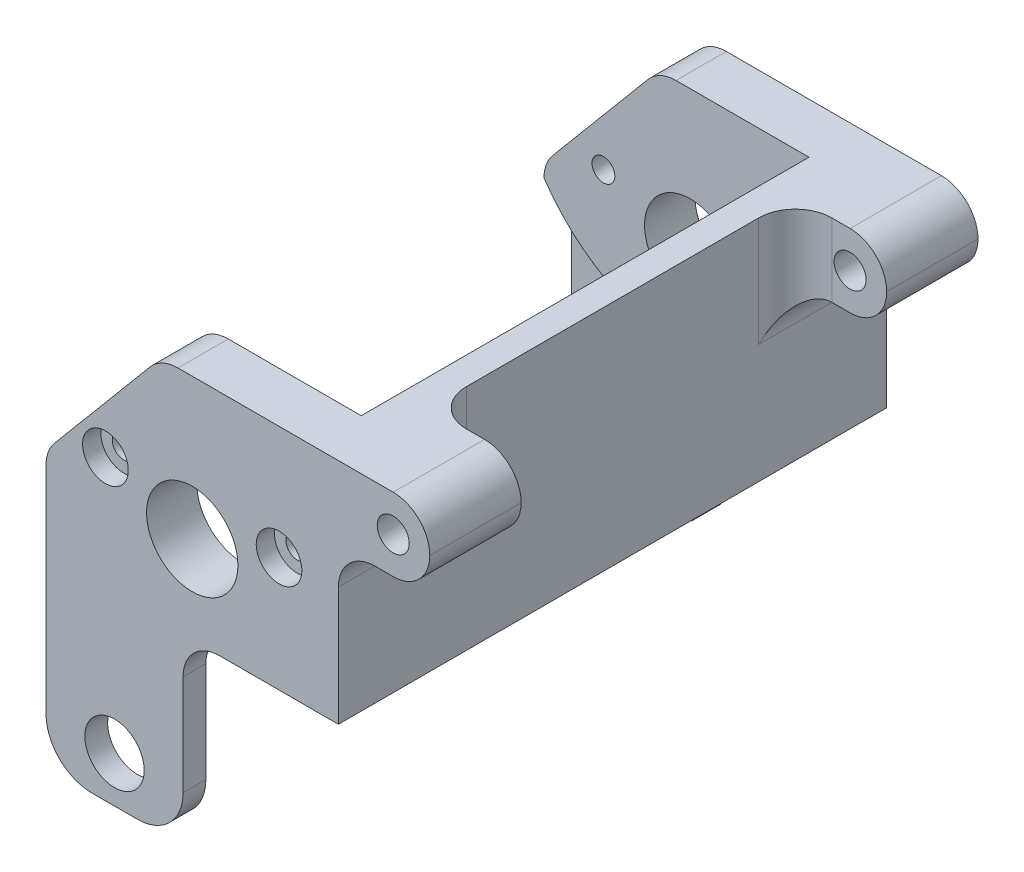
SolidWorks part; units mm, degrees
ref_plane "Front Plane" through (0, 0, 0) normal (0, 0, 1) x (1, 0, 0)
ref_plane "Top Plane" through (0, 0, 0) normal (0, 1, 0) x (1, 0, 0)
ref_plane "Right Plane" through (0, 0, 0) normal (1, 0, 0) x (0, 0, -1)
sketch "Sketch2" plane through (0, 0, 0) normal (0, 0, 1) x (1, 0, 0)
  line L0 (-7.5, 5) -> (-7.5, 30)
  line L1 (-7.5, 30) -> (5.0865, 45)
  line L2 (5.0865, 45) -> (24.5, 45)
  line L3 (24.5, 45) -> (24.5, 20)
  line L4 (24.5, 20) -> (7.5, 20)
  line L5 (7.5, 20) -> (7.5, 5)
  line L6 (-2.5, 0) -> (2.5, 0)
  line L7 (-7.5, 0) -> (7.5, 0) construction
  line L8 (-7.5, 5) -> (7.5, 5) construction
  line L9 (18.0048, 32.5697) -> (-0.9952, 32.5697) construction
  line L10 (8.5048, 32.5697) -> (8.5048, 29.5697) construction
  line L11 (0, 5) -> (8.5048, 29.5697) construction
  circle A5 centre (0, 5) radius 3.25
  circle A6 centre (18.0048, 32.5697) radius 1.25
  circle A7 centre (-0.9952, 32.5697) radius 1.25
  circle A8 centre (8.5048, 29.5697) radius 5
  circle A9 centre (8.5048, 32.5697) radius 12.5 construction
  arc A10 (2.5, 0) -> (7.5, 5) centre (2.5, 5) ccw
  arc A11 (-7.5, 5) -> (-2.5, 0) centre (-2.5, 5) ccw
  dimension "D3" = 6.5
  dimension "D4" = 5
  dimension "D10" = 10
  dimension "D12" = 2.5
  dimension "D14" = 25
  dimension "D15" = 5
  dimension "D1" = 40
  dimension "D2" = 15
  dimension "D5" = 30
  dimension "D6" = 15
  dimension "D7" = 17
  dimension "D8" = 20
  dimension "D9" = 19
  dimension "D11" = 3
  dimension "D13" = 26
extrude "Boss-Extrude1" add sketch "Sketch2" along normal blind 30 and the other way blind 30
sketch "Sketch3" plane through (0, 45, 0) normal (0, 1, 0) x (1, 0, 0)
  line L0 (-7.5, -30) -> (-7.5, 30) construction
  line L1 (-36.5, -27.5) -> (21.5, -27.5)
  line L2 (-36.5, -27.5) -> (-36.5, 27.5)
  line L3 (-36.5, 27.5) -> (21.5, 27.5)
  line L4 (21.5, -27.5) -> (21.5, 27.5)
  line L5 (-36.5, -27.5) -> (21.5, 27.5) construction
  line L6 (-36.5, 27.5) -> (21.5, -27.5) construction
  line L7 (24.5, 30) -> (5.0865, 30) construction
  line L8 (24.5, -30) -> (24.5, 30) construction
  point P0 (-7.5, 0)
  dimension "D1" = 2.5
  dimension "D2" = 3
extrude "Cut-Extrude1" cut sketch "Sketch3" against normal through all
sketch "Sketch4" plane through (24.5, 0, 0) normal (1, 0, 0) x (0, 0, -1)
  line L1 (-30, 45) -> (-20, 45)
  line L2 (-30, 45) -> (-30, 37)
  line L3 (-30, 37) -> (-20, 37)
  line L4 (-20, 45) -> (-20, 37)
  dimension "D1" = 10
  dimension "D2" = 8
extrude "Boss-Extrude2" add sketch "Sketch4" along normal blind 10
fillet "Fillet1" radius 4 2 edges at (34.5, 37, 25) (34.5, 45, 25)
sketch "Sketch5" plane through (0, 0, 20) normal (0, 0, -1) x (-1, 0, 0)
  circle A0 centre (-30.5, 41) radius 1.75
  dimension "D1" = 3.5
extrude "Cut-Extrude2" cut sketch "Sketch5" against normal through all
mirror "Mirror1" about plane through (0, 0, 0) normal (0, 0, 1) of "Cut-Extrude2", "Fillet1", "Boss-Extrude2"
fillet "Fillet2" radius 4 10 edges at (24.5, 41, -20) (24.5, 41, 20) (5.0865, 45, -28.75) (7.5, 20, -28.75) (24.5, 37, -25) (24.5, 37, 25) (7.5, 20, 28.75) (5.0865, 45, 28.75) (-7.5, 30, 28.75) (-7.5, 30, -28.75)
sketch "Sketch6" plane through (0, 0, -27.5) normal (0, 0, 1) x (1, 0, 0)
  line L0 (-0.9952, 32.5697) -> (18.0048, 32.5697) construction
  line L7 (21.5, 45) -> (6.9517, 45)
  line L8 (3.8875, 43.5712) -> (-6.5642, 31.1153)
  line L9 (-7.5, 28.5441) -> (-7.5, 5)
  line L10 (-2.5, 0) -> (2.5, 0)
  line L11 (7.5, 5) -> (7.5, 16)
  line L12 (11.5, 20) -> (21.5, 20)
  line L13 (21.5, 20) -> (21.5, 45)
  line L14 (21.5, 45) -> (6.9517, 45)
  line L15 (3.8875, 43.5712) -> (-6.5642, 31.1153)
  line L19 (11.5, 20) -> (21.5, 20)
  line L20 (21.5, 20) -> (21.5, 45)
  arc A1 (11.5, 20) -> (-7.5, 28.5441) centre (8.8465, 39.497) cw
  circle A2 centre (18.0048, 32.5697) radius 1.25 construction
  circle A3 centre (8.5048, 29.5697) radius 5 construction
  circle A4 centre (-0.9952, 32.5697) radius 1.25 construction
  circle A5 centre (18.0048, 32.5697) radius 1.25
  arc A6 (6.9517, 45) -> (3.8875, 43.5712) centre (6.9517, 41) ccw
  arc A7 (-6.5642, 31.1153) -> (-7.5, 28.5441) centre (-3.5, 28.5441) ccw
  arc A8 (-7.5, 5) -> (-2.5, 0) centre (-2.5, 5) ccw
  arc A9 (2.5, 0) -> (7.5, 5) centre (2.5, 5) ccw
  arc A10 (11.5, 20) -> (7.5, 16) centre (11.5, 16) ccw
  arc A11 (6.9517, 45) -> (3.8875, 43.5712) centre (6.9517, 41) ccw
  arc A12 (-6.5642, 31.1153) -> (-7.5, 28.5441) centre (-3.5, 28.5441) ccw
  circle A16 centre (8.5048, 29.5697) radius 5
  circle A17 centre (-0.9952, 32.5697) radius 1.25
  dimension "D1" = 0
extrude "Boss-Extrude3" add sketch "Sketch6" along normal blind 3
sketch "Sketch7" plane through (0, 0, -30) normal (0, 0, -1) x (-1, 0, 0)
  circle A0 centre (-18.0048, 32.5697) radius 2.5
  circle A1 centre (0.9952, 32.5697) radius 2.5
  dimension "D1" = 5
extrude "Cut-Extrude3" cut sketch "Sketch7" against normal blind 2
mirror "Mirror2" about plane through (0, 0, 0) normal (0, 0, 1) of "Cut-Extrude3", "Boss-Extrude3"
